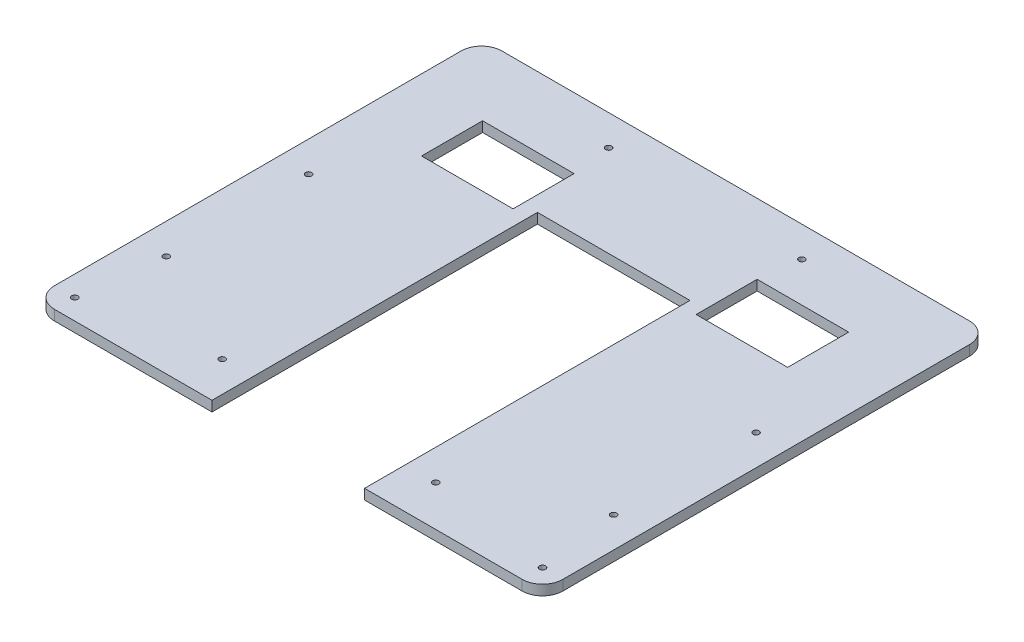
SolidWorks part; units mm, degrees
ref_plane "前视基准面" through (0, 0, 0) normal (0, 0, 1) x (1, 0, 0)
ref_plane "上视基准面" through (0, 0, 0) normal (0, 1, 0) x (1, 0, 0)
ref_plane "右视基准面" through (0, 0, 0) normal (1, 0, 0) x (0, 0, -1)
sketch "草图1" plane through (0, 0, 0) normal (0, 1, 0) x (1, 0, 0)
  line L1 (10, 0) -> (240, 0)
  line L2 (0, -10) -> (0, -210)
  line L3 (10, -220) -> (240, -220)
  line L4 (250, -10) -> (250, -210)
  arc A0 (0, -210) -> (10, -220) centre (10, -210) ccw
  arc A1 (240, -220) -> (250, -210) centre (240, -210) ccw
  arc A2 (240, 0) -> (250, -10) centre (240, -10) cw
  arc A3 (10, 0) -> (0, -10) centre (10, -10) ccw
  point P9 (250, -220)
  point P12 (250, 0)
  point P15 (0, 0)
  dimension "D3" = 10
  dimension "D1" = 250
  dimension "D2" = 220
extrude "凸台-拉伸1" add sketch "草图1" along normal blind 5
sketch "草图2" plane through (0, 0, 0) normal (0, -1, 0) x (1, 0, 0)
  line L0 (239.1778, 11.85) -> (239.1778, 76.15) construction
  line L1 (239.1778, 11.85) -> (239.1778, 76.15)
  line L2 (250, 210) -> (250, 10) construction
  line L3 (239.1778, 76.15) -> (250, 76.15)
  line L4 (239.1778, 76.15) -> (239.1778, 0)
  line L5 (239.1778, 0) -> (250, 0)
  line L6 (250, 76.15) -> (250, 0)
  line L7 (125, 220) -> (125, 0) construction
  line L8 (10, 220) -> (240, 220) construction
  line L9 (240, 0) -> (10, 0) construction
  line L10 (0, 76.15) -> (0, 0)
  line L11 (10.8222, 0) -> (0, 0)
  line L12 (10.8222, 76.15) -> (10.8222, 0)
  line L13 (10.8222, 76.15) -> (0, 76.15)
sketch "草图4" plane through (0, 0, 0) normal (0, -1, 0) x (1, 0, 0)
  line L1 (125, 0) -> (125, 220) construction
  line L2 (240, 0) -> (10, 0) construction
  line L3 (10, 220) -> (240, 220) construction
  line L8 (170, 64.475) -> (170, 34.475)
  line L16 (215, 34.475) -> (170, 34.475)
  line L17 (215, 64.475) -> (215, 34.475)
  line L18 (215, 64.475) -> (170, 64.475)
  line L19 (209.9, 64.475) -> (215, 64.475)
  line L20 (215, 64.475) -> (215, 46.825)
  line L21 (204.1, 64.475) -> (199, 64.475)
  line L22 (209.9, 64.475) -> (215, 64.475)
  line L23 (204.1, 64.475) -> (199, 64.475)
  line L24 (40.1, 64.475) -> (45.9, 64.475)
  line L25 (35, 64.475) -> (35, 46.825)
  line L26 (45.9, 64.475) -> (51, 64.475)
  line L27 (215, 64.475) -> (215, 46.825)
  line L28 (209.9, 64.475) -> (204.1, 64.475)
  line L29 (0, 10) -> (0, 210) construction
  line L30 (40.1, 64.475) -> (35, 64.475)
  line L31 (45.9, 64.475) -> (51, 64.475)
  line L33 (35, 64.475) -> (35, 46.825)
  line L35 (40.1, 64.475) -> (35, 64.475)
  line L38 (35, 64.475) -> (80, 64.475)
  line L39 (35, 64.475) -> (35, 34.475)
  line L120 (35, 34.475) -> (80, 34.475)
  line L121 (80, 64.475) -> (80, 34.475)
  dimension "D3" = 45
  dimension "D4" = 30
  dimension "D1" = 35
extrude "切除-拉伸3" cut sketch "草图4" against normal blind 5 contours L24 L30 L25 L26 | L18 L8 L16 L17 region at (57.5, 0, 49.475)
sketch "草图5" plane through (0, 0, 0) normal (0, -1, 0) x (1, 0, 0)
  line L0 (125, 220) -> (125, 0) construction
  line L1 (10, 220) -> (240, 220) construction
  line L2 (240, 0) -> (10, 0) construction
  line L3 (87.5, 220) -> (162.5, 220) construction
  line L4 (87.5, 220) -> (87.5, 60)
  line L5 (162.5, 220) -> (87.5, 220)
  line L6 (162.5, 220) -> (162.5, 60)
  line L7 (162.5, 60) -> (87.5, 60)
  point P11 (125, 60)
  dimension "D1" = 37.5
  dimension "D2" = 160
extrude "切除-拉伸4" cut sketch "草图5" against normal blind 5
sketch "草图6" plane through (0, 0, 0) normal (0, -1, 0) x (1, 0, 0)
  line L0 (72.5, 220) -> (72.5, 200) construction
  line L1 (10, 220) -> (87.5, 220) construction
  line L2 (72.5, 200) -> (87.5, 200) construction
  line L7 (87.5, 220) -> (87.5, 60) construction
  line L8 (125, 60) -> (125, 181.8158) construction
  line L9 (87.5, 60) -> (162.5, 60) construction
  line L10 (87.5, 60) -> (87.5, 0) construction
  line L11 (240, 0) -> (10, 0) construction
  line L12 (87.5, 20) -> (92.5, 20) construction
  line L13 (92.5, 20) -> (92.5, 0) construction
  line L14 (92.5, 20) -> (107.5, 20) construction
  circle A0 centre (72.5, 200) radius 1.5
  circle A3 centre (177.5, 200) radius 1.5
  dimension "D3" = 3
  dimension "D1" = 20
  dimension "D2" = 15
  dimension "D4" = 5
  dimension "D5" = 20
  dimension "D6" = 15
extrude "切除-拉伸5" cut sketch "草图6" against normal up to next contours A0 | A3
sketch "草图7" plane through (0, 0, 0) normal (0, -1, 0) x (1, 0, 0)
  line L0 (17, 15) -> (17, 73) construction
  line L1 (25, 29) -> (25, 59) construction
  line L2 (17, 44) -> (25, 44) construction
  line L3 (240, 0) -> (10, 0) construction
  line L5 (125, 60) -> (125, 0) construction
  line L6 (87.5, 60) -> (162.5, 60) construction
  line L8 (233, 44) -> (225, 44) construction
  line L9 (225, 29) -> (225, 59) construction
  line L10 (233, 15) -> (233, 73) construction
  line L11 (0, 10) -> (0, 210) construction
  circle A0 centre (17, 15) radius 1.6
  circle A1 centre (25, 29) radius 1.6
  circle A2 centre (25, 59) radius 1.6
  circle A3 centre (17, 73) radius 1.6
  circle A4 centre (233, 73) radius 1.6
  circle A5 centre (225, 59) radius 1.6
  circle A6 centre (225, 29) radius 1.6
  circle A7 centre (233, 15) radius 1.6
  dimension "D1" = 8
  dimension "D2" = 58
  dimension "D3" = 30
  dimension "D4" = 58
  dimension "D5" = 17
  dimension "D6" = 15
sketch "草图8" plane through (0, 0, 0) normal (0, -1, 0) x (1, 0, 0)
  line L0 (250, 170) -> (235, 170) construction
  line L1 (250, 210) -> (250, 10) construction
  line L2 (235, 170) -> (235, 220) construction
  line L3 (162.5, 220) -> (240, 220) construction
  line L4 (235, 170) -> (235, 100) construction
  line L5 (235, 100) -> (250, 100) construction
  line L6 (125, 60) -> (125, 122.441) construction
  line L7 (87.5, 60) -> (162.5, 60) construction
  line L8 (15, 170) -> (15, 100) construction
  circle A0 centre (235, 170) radius 1.5
  circle A1 centre (235, 100) radius 1.5
  circle A2 centre (15, 100) radius 1.5
  circle A3 centre (15, 170) radius 1.5
  dimension "D4" = 3
  dimension "D5" = 3
  dimension "D1" = 15
  dimension "D2" = 50
  dimension "D3" = 70
extrude "切除-拉伸8" cut sketch "草图8" against normal up to next
sketch "草图9" plane through (0, 0, 0) normal (0, -1, 0) x (1, 0, 0)
  line L0 (87.5, 60) -> (87.5, 0) construction
  line L1 (240, 0) -> (10, 0) construction
  line L2 (87.5, 0) -> (87.5, 15) construction
  line L3 (87.5, 15) -> (77.5, 15) construction
  line L4 (10, 220) -> (10, 210) construction
  line L5 (125, 60) -> (125, 0) construction
  line L6 (87.5, 60) -> (162.5, 60) construction
  circle A0 centre (77.5, 15) radius 1.5
  circle A1 centre (10, 210) radius 1.5
  circle A2 centre (240, 210) radius 1.5
  circle A3 centre (172.5, 15) radius 1.5
  dimension "D3" = 3
  dimension "D4" = 3
  dimension "D1" = 15
  dimension "D2" = 10
extrude "切除-拉伸9" cut sketch "草图9" against normal up to next
sketch "草图10" plane through (0, 0, 0) normal (0, -1, 0) x (1, 0, 0)
  line L0 (125, 60) -> (125, 0) construction
  line L1 (0, 0) -> (8, 0)
  line L2 (0, 0) -> (0, 85)
  line L3 (0, 85) -> (8, 85)
  line L4 (8, 0) -> (8, 85)
  line L5 (87.5, 60) -> (162.5, 60) construction
  line L6 (240, 0) -> (10, 0) construction
  line L7 (242, 0) -> (242, 85)
  line L8 (250, 85) -> (242, 85)
  line L9 (250, 0) -> (250, 85)
  line L10 (250, 0) -> (242, 0)
  dimension "D1" = 8
  dimension "D2" = 85
